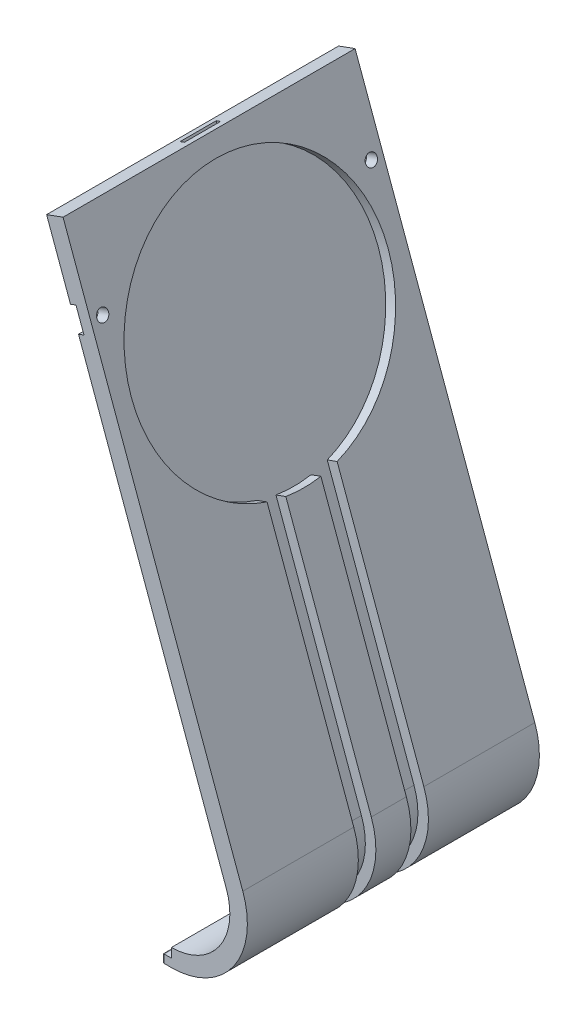
SolidWorks part; units mm, degrees
material "PLA"
ref_plane "前视基准面" through (0, 0, 0) normal (0, 0, 1) x (1, 0, 0)
ref_plane "上视基准面" through (0, 0, 0) normal (0, 1, 0) x (1, 0, 0)
ref_plane "右视基准面" through (0, 0, 0) normal (1, 0, 0) x (0, 0, -1)
other "Configuration Table"
sketch "草图2" plane through (0, 0, 0) normal (0, 0, 1) x (1, 0, 0)
  line L0 (38.2711, 18.4699) -> (5.8755, 107.4762) construction
  line L5 (38.2711, 18.4699) -> (7.4967, 103.022)
  line L6 (6.4731, 108.7579) -> (8.8224, 109.6129) construction
  line L10 (28.8742, 5.0497) -> (28.8742, 4.0497) construction
  arc A0 (28.8742, 5.0497) -> (38.2711, 18.4699) centre (28.8742, 15.0497) ccw
  arc A1 (28.8742, 5.0497) -> (38.2711, 18.4699) centre (28.8742, 15.0497) ccw construction
  dimension "D2" = 10
  dimension "D1" = 5.74
extrude "整体拉伸-薄壁1" add sketch "草图2" along normal mid plane 50 thin thin type one direction wall 3
sketch "草图4" plane through (42.5494, 15.4867, 0) normal (0.9397, 0.342, 0) x (0, 0, -1)
  line L0 (-25, 94.245) -> (25, 94.245) construction
  circle A0 centre (0, 68.845) radius 22
  dimension "D1" = 44
  dimension "D2" = 25.4
extrude "中间圆切除-拉伸1" cut sketch "草图4" against normal blind 1.8
sketch "草图3" plane through (0, 0, 0) normal (0, 0, 1) x (1, 0, 0)
  line L0 (41.0902, 19.4959) -> (10.3157, 104.0481) construction
  line L1 (41.0902, 19.4959) -> (10.3157, 104.0481) construction
  line L2 (28.8742, 2.0497) -> (28.8742, 5.0497) construction
  line L5 (39.3988, 18.8803) -> (24.836, 58.891)
  line L6 (39.3988, 18.8803) -> (8.6243, 103.4325) construction
  line L7 (28.8742, 3.8497) -> (28.8742, 3.8497) construction
  line L9 (24.836, 58.891) -> (26.5275, 59.5067) construction
  line L16 (24.836, 58.891) -> (23.81, 61.7101)
  line L17 (27.0769, 3.9492) -> (17.8463, 8.166) construction
  arc A0 (28.8742, 5.0497) -> (38.2711, 18.4699) centre (28.8742, 15.0497) ccw construction
  arc A1 (17.8463, 8.166) -> (41.0902, 19.4959) centre (28.8742, 15.0497) ccw construction
  arc A2 (28.8742, 3.8497) -> (39.3988, 18.8803) centre (28.8742, 15.0497) ccw
  dimension "D2" = 3
  dimension "D1" = 1.8
extrude "线槽切除-拉伸-薄壁1" cut sketch "草图3" against normal blind 3 from offset 6 thin thin type one direction wall 1.8
mirror "镜向1" about plane through (0, 0, 0) normal (0, 0, 1) of "线槽切除-拉伸-薄壁1"
sketch "草图11" plane through (28.8742, 0, 0) normal (-1, 0, 0) x (0, 0, 1)
  line L0 (-25, 2.0497) -> (-25, 5.0497) construction
  line L1 (-25, 3.4497) -> (-6.1, 3.4497)
  line L2 (-25, 3.4497) -> (-25, 2.0497)
  line L3 (-25, 2.0497) -> (-6.1, 2.0497)
  line L4 (-6.1, 3.4497) -> (-6.1, 2.0497)
  line L5 (25, 2.0497) -> (6, 2.0497) construction
  line L6 (6.1, 3.4497) -> (25, 3.4497)
  line L7 (6.1, 3.4497) -> (6.1, 2.0497)
  line L8 (6.1, 2.0497) -> (25, 2.0497)
  line L9 (25, 3.4497) -> (25, 2.0497)
  line L11 (-6, 2.0497) -> (-6, 3.8497) construction
  line L13 (6, 2.0497) -> (6, 3.8497) construction
  line L14 (25, 5.0497) -> (-25, 5.0497) construction
  dimension "D1" = 1.6
  dimension "D2" = 0.1
  dimension "D3" = 0.1
  dimension "D4" = 1.6
extrude "底部卡扣凸台-拉伸3" add sketch "草图11" along normal blind 1.5
fillet "底部卡扣圆角1" radius 0.25 8 edges at (27.3742, 3.4497, 15.55) (27.3742, 2.7497, 25) (27.3742, 2.0497, 15.55) (27.3742, 2.7497, 6.1) (27.3742, 3.4497, -15.55) (27.3742, 2.7497, -6.1) (27.3742, 2.0497, -15.55) (27.3742, 2.7497, -25)
sketch "草图12" plane through (39.7304, 14.4607, 0) normal (-0.9397, -0.342, 0) x (0, 0, 1)
  line L0 (-36.5, 82.2828) -> (36.5, 82.2828) construction
  line L2 (-25, 4.2665) -> (-25, 94.245) construction
  line L3 (25, 4.2665) -> (25, 94.245) construction
  circle A0 centre (23, 80.2828) radius 1
  circle A1 centre (-23, 80.2828) radius 1
  dimension "D1" = 2
  dimension "D2" = 2
  dimension "D3" = 2
  dimension "D4" = 2
  dimension "D5" = 2
  dimension "D6" = 2
extrude "螺丝孔" cut sketch "草图12" against normal through all
sketch "草图13" plane through (39.7304, 14.4607, 0) normal (-0.9397, -0.342, 0) x (0, 0, 1)
  line L0 (25, 4.2665) -> (25, 94.245) construction
  line L1 (23, 82.2828) -> (25, 82.2828)
  line L3 (23, 78.2828) -> (25, 78.2828)
  line L4 (25, 82.2828) -> (25, 78.2828)
  line L5 (-36.5, 82.2828) -> (36.5, 82.2828) construction
  line L6 (0, 94.245) -> (0, 78.3622) construction
  line L7 (25, 94.245) -> (-25, 94.245) construction
  line L8 (-25, 82.2828) -> (-25, 78.2828)
  line L9 (-23, 78.2828) -> (-25, 78.2828)
  line L10 (-23, 82.2828) -> (-25, 82.2828)
  arc A0 (23, 82.2828) -> (23, 78.2828) centre (23, 80.2828) ccw
  arc A1 (-23, 82.2828) -> (-23, 78.2828) centre (-23, 80.2828) cw
  dimension "D1" = 4
extrude "切除-拉伸1" cut sketch "草图13" against normal blind 1
sketch "草图14" plane through (-32.2337, 88.5614, 0) normal (-0.342, 0.9397, 0) x (0.9397, 0.342, 0)
  line L0 (42.2802, -5.1) -> (45.2802, -5.1) construction
  line L1 (44.0802, 3.1) -> (43.2802, 3.1)
  line L2 (44.0802, 3.1) -> (44.0802, -3.1)
  line L3 (44.0802, -3.1) -> (43.2802, -3.1)
  line L4 (43.2802, 3.1) -> (43.2802, -3.1)
  line L5 (45.2802, 5.1) -> (42.2802, 5.1) construction
  line L6 (42.2802, -25) -> (42.2802, 25) construction
  line L7 (45.2802, -25) -> (45.2802, 25) construction
  dimension "D1" = 2
  dimension "D2" = 2
  dimension "D3" = 1
  dimension "D4" = 1.2
extrude "切除-拉伸2" cut sketch "草图14" against normal blind 1
